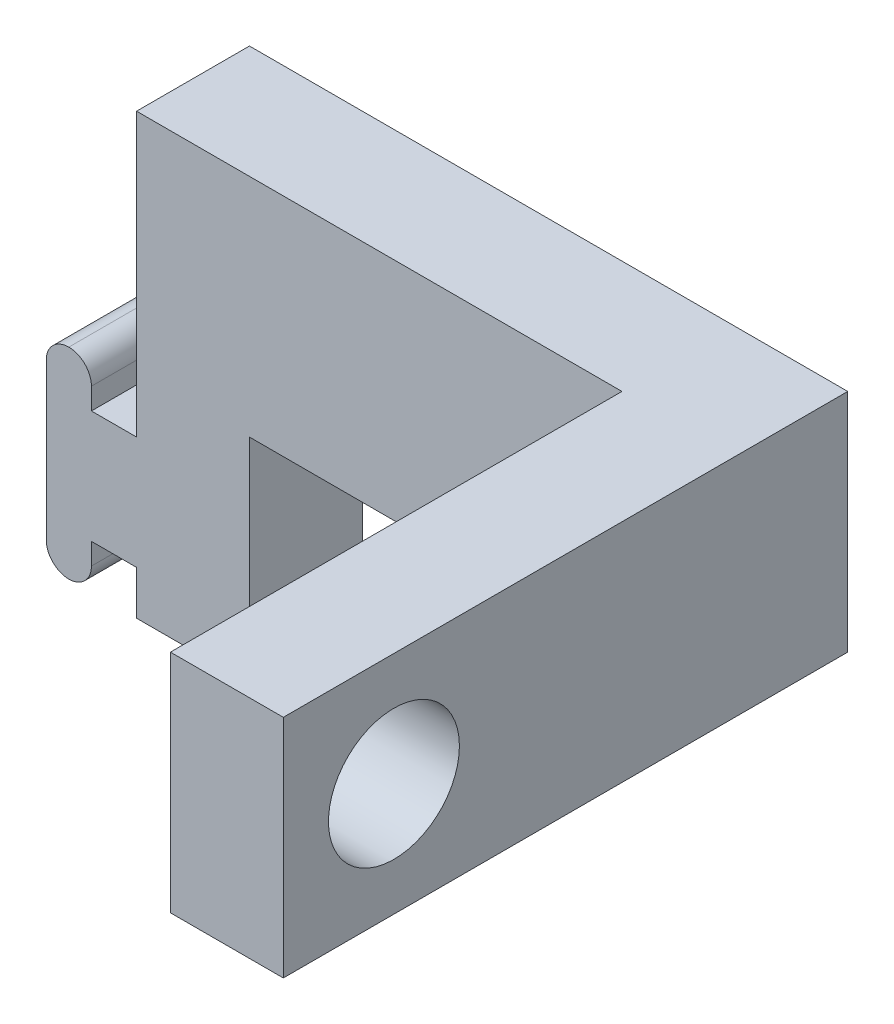
SolidWorks part; units mm, degrees
ref_plane "Front Plane" through (0, 0, 0) normal (0, 0, 1) x (1, 0, 0)
ref_plane "Top Plane" through (0, 0, 0) normal (0, 1, 0) x (1, 0, 0)
ref_plane "Right Plane" through (0, 0, 0) normal (1, 0, 0) x (0, 0, -1)
sketch "Sketch1" plane through (0, 0, 0) normal (0, 1, 0) x (1, 0, 0)
  line L0 (0, 0) -> (0, 31.75)
  line L1 (0, 31.75) -> (-22.86, 31.75)
  line L2 (-22.86, 31.75) -> (-22.86, 25.4)
  line L3 (-22.86, 25.4) -> (-6.35, 25.4)
  line L4 (-6.35, 25.4) -> (-6.35, 0)
  line L5 (-6.35, 0) -> (0, 0)
  dimension "D1" = 25.4
  dimension "D2" = 16.51
  dimension "D3" = 6.35
  dimension "D4" = 6.35
extrude "Boss-Extrude1" add sketch "Sketch1" along normal blind 12.7
sketch "Sketch3" plane through (0, 0, -31.75) normal (0, 0, -1) x (-1, 0, 0)
  line L0 (22.86, 12.7) -> (33.655, 12.7)
  line L3 (38.735, -0.6985) -> (38.735, -12.0015)
  line L5 (27.305, -12.0015) -> (27.305, 0)
  line L6 (0, 0) -> (22.86, 0) construction
  line L7 (27.305, 0) -> (22.86, 0)
  line L8 (22.86, 0) -> (22.86, 12.7)
  line L9 (27.305, -12.0015) -> (33.655, -12.0015)
  line L10 (33.655, -12.0015) -> (33.655, -9.525)
  line L11 (33.655, -9.525) -> (36.195, -9.525)
  line L12 (36.195, -9.525) -> (36.195, -12.0015)
  line L13 (36.195, -12.0015) -> (38.735, -12.0015)
  line L15 (33.655, 12.7) -> (33.655, -3.175)
  line L16 (33.655, -3.175) -> (36.195, -3.175)
  line L17 (36.195, -3.175) -> (36.195, -0.6985)
  line L18 (36.195, -0.6985) -> (38.735, -0.6985)
  line L19 (36.195, -9.525) -> (36.195, -3.175) construction
  point P3 (36.195, -6.35)
  point P4 (38.735, -6.35)
  point P17 (22.86, 6.35)
  dimension "D1" = 2.54
  dimension "D2" = 11.303
  dimension "D3" = 6.35
  dimension "D4" = 12.7
  dimension "D5" = 2.54
  dimension "D6" = 27.305
  dimension "D7" = 6.35
extrude "Boss-Extrude2" add sketch "Sketch3" against normal blind 6.35
fillet "Fillet1" radius 1.27 1 edges at (-36.195, -0.6985, -28.575)
fillet "Fillet2" radius 1.27 3 edges at (-36.195, -12.0015, -28.575) (-38.735, -12.0015, -28.575) (-38.735, -0.6985, -28.575)
sketch "Sketch4" plane through (0, 0, 0) normal (0, 0, 1) x (1, 0, 0)
  line L1 (-6.35, 0) -> (0, 0)
  line L2 (-6.35, 0) -> (-6.35, 12.7)
  line L3 (-6.35, 12.7) -> (0, 12.7)
  line L4 (0, 0) -> (0, 12.7)
sketch "Sketch5" plane through (0, 0, 0) normal (1, 0, 0) x (0, 0, -1)
  circle A0 centre (6.223, 6.35) radius 3.683
  dimension "D1" = 19.177
extrude "Cut-Extrude1" cut sketch "Sketch5" against normal through all both and the other way through all
